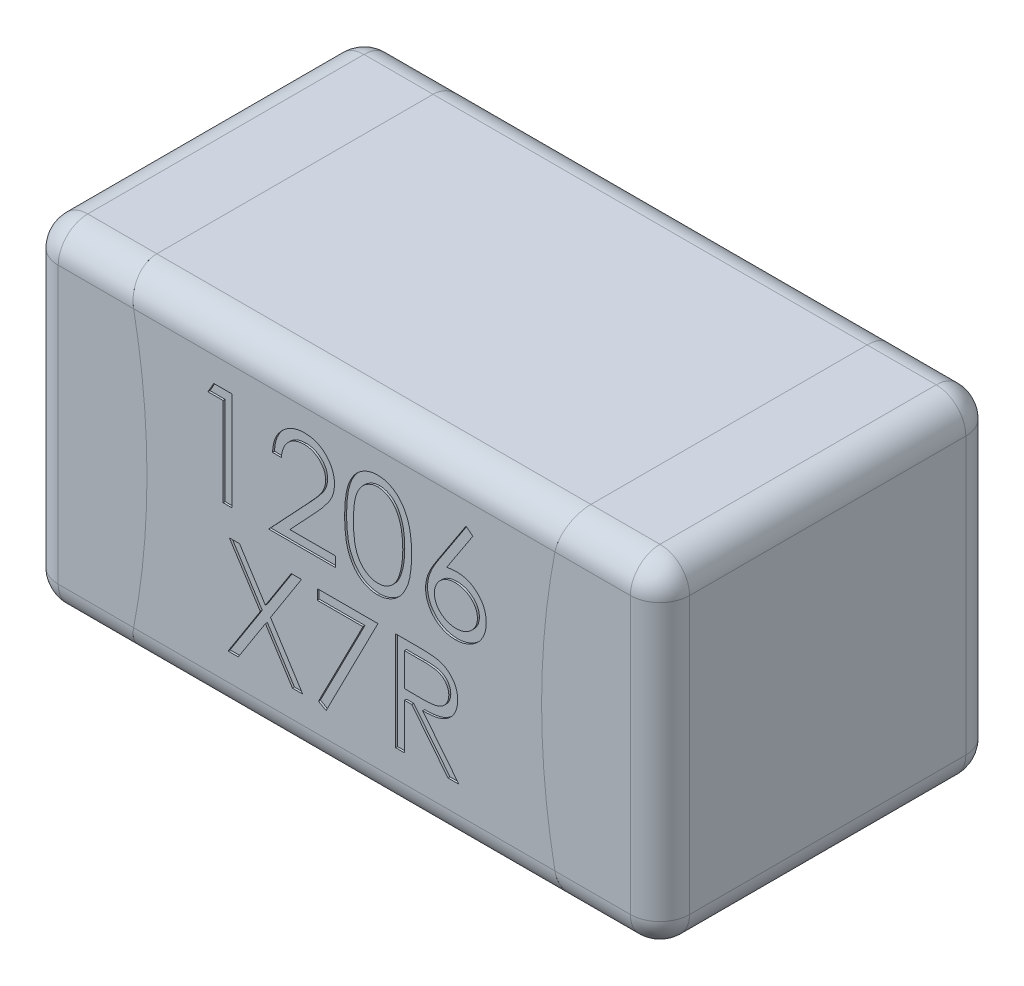
SolidWorks part; units mm, degrees
ref_plane "Спереди" through (0, 0, 0) normal (0, 0, 1) x (1, 0, 0)
ref_plane "Сверху" through (0, 0, 0) normal (0, 1, 0) x (1, 0, 0)
ref_plane "Справа" through (0, 0, 0) normal (1, 0, 0) x (0, 0, -1)
sketch "Эскиз1" plane through (0, 0, 0) normal (0, 0, 1) x (1, 0, 0)
  line L0 (1.6, 0.85) -> (-1.6, -0.85) construction
  line L1 (-1.6, 0.85) -> (1.6, 0.85)
  line L2 (-1.6, 0.85) -> (-1.6, -0.85)
  line L3 (-1.6, -0.85) -> (1.6, -0.85)
  line L4 (1.6, 0.85) -> (1.6, -0.85)
  line L5 (1.1, 0.85) -> (1.1, -0.85) construction
  line L6 (-1, 0) -> (-1.6, 0) construction
  line L7 (-1.1, 0.85) -> (-1.1, -0.85) construction
  line L9 (1, 0) -> (1.6, 0) construction
  arc A0 (-1.1, 0.85) -> (-1.1, -0.85) centre (-4.6625, 0) cw
  arc A1 (1.1, 0.85) -> (1.1, -0.85) centre (4.6625, 0) ccw
  dimension "D1" = 3.2
  dimension "D2" = 1.7
  dimension "D3" = 0.6
  dimension "D4" = 0.6
  dimension "D5" = 0.5
extrude "Бобышка-Вытянуть1" add sketch "Эскиз1" along normal blind 1.7 contours A0 L1 L2 L3 | L1 A1 L3 L4 region at (-1.3158, 0, 0) region at (1.3158, 0, 0)
extrude "Бобышка-Вытянуть2" add sketch "Эскиз1<3>" along normal blind 1.7 separate body contours A1 L1 A0 L3 region at (0, 0, 0)
sketch "Эскиз1<3>" plane through (0, 0, 0) normal (0, 0, 1) x (1, 0, 0) same geometry as "Эскиз1"
fillet "Скругление1" radius 0.15 8 edges at (1.6, -0.85, 0.85) (1.6, 0, 1.7) (1.6, 0.85, 0.85) (1.6, 0, 0) (1.35, -0.85, 0) (1.35, -0.85, 1.7) (1.35, 0.85, 0) (1.35, 0.85, 1.7)
fillet "Скругление2" radius 0.15 8 edges at (-1.6, 0.85, 0.85) (-1.6, 0, 1.7) (-1.6, -0.85, 0.85) (-1.6, 0, 0) (-1.35, 0.85, 0) (-1.35, -0.85, 0) (-1.35, 0.85, 1.7) (-1.35, -0.85, 1.7)
fillet "Скругление3" radius 0.15 4 edges at (0, -0.85, 1.7) (0, -0.85, 0) (0, 0.85, 1.7) (0, 0.85, 0)
sketch "Эскиз2" plane through (0, 0, 1.7) normal (0, 0, 1) x (1, 0, 0)
  text T0 "1206" font "Century Gothic" height 0.5
  text T1 "X7R" font "Century Gothic" height 0.5
extrude "Вырез-Вытянуть1" cut sketch "Эскиз2" against normal blind 0.01
